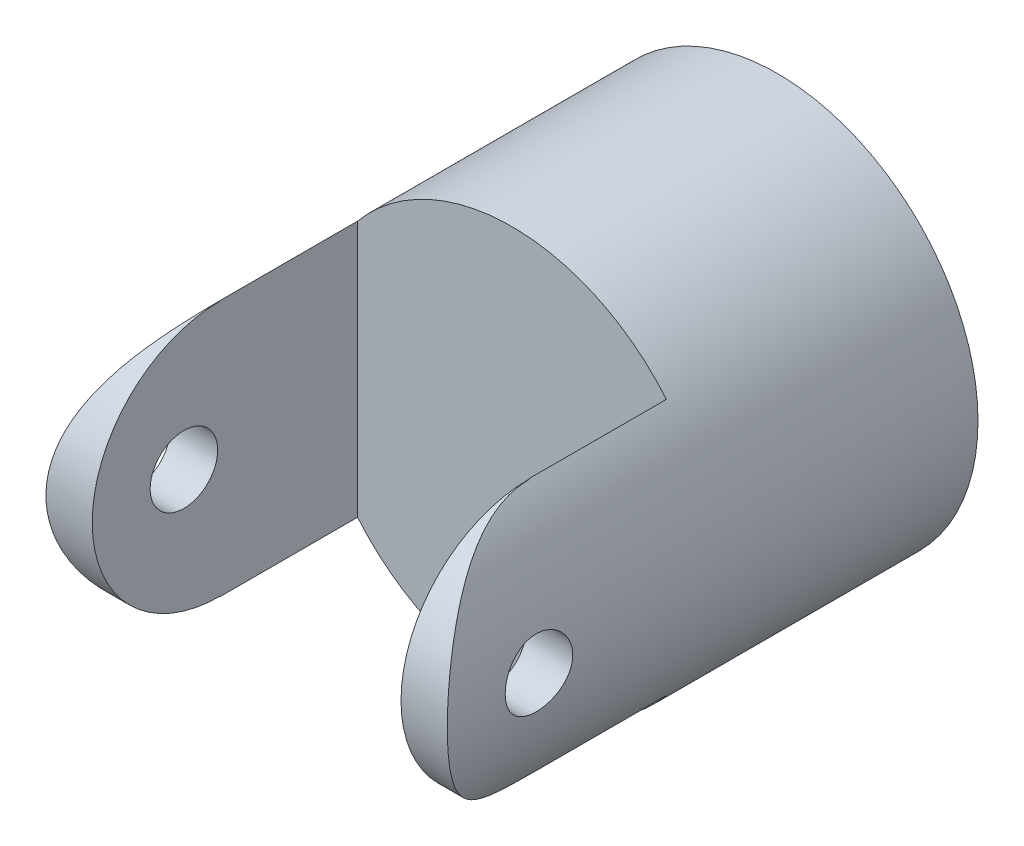
SolidWorks part; units mm, degrees
ref_plane "Front Plane" through (0, 0, 0) normal (0, 0, 1) x (1, 0, 0)
ref_plane "Top Plane" through (0, 0, 0) normal (0, 1, 0) x (1, 0, 0)
ref_plane "Right Plane" through (0, 0, 0) normal (1, 0, 0) x (0, 0, -1)
sketch "Sketch1" plane through (0, 0, 0) normal (0, 0, 1) x (1, 0, 0)
  circle A0 centre (0, 0) radius 4.16
  dimension "D1" = 8.32
extrude "Extrude1" add sketch "Sketch1" along normal blind 11
sketch "Sketch2" plane through (0, 0, 0) normal (0, 1, 0) x (1, 0, 0)
  line L0 (-4.16, 0) -> (-4.16, -11) construction
  line L1 (-3.2, -11.8574) -> (3.2, -11.8574)
  line L2 (-3.2, -11.8574) -> (-3.2, -5.5)
  line L3 (-3.2, -5.5) -> (3.2, -5.5)
  line L4 (3.2, -11.8574) -> (3.2, -5.5)
  line L5 (-4.16, -11) -> (4.16, -11) construction
  dimension "D1" = 6.4
  dimension "D2" = 0.96
  dimension "D3" = 5.5
extrude "Extrude2" cut sketch "Sketch2" against normal through all and the other way through all
sketch "Sketch3" plane through (0, 0, 0) normal (1, 0, 0) x (0, 0, -1)
  line L2 (-8.35, 2.65) -> (-8.35, 3.8367)
  line L4 (-8.35, -4.4922) -> (-12.8222, -4.6052)
  line L5 (-12.8222, -4.6052) -> (-12.8222, 3.8367)
  line L6 (-12.8222, 3.8367) -> (-8.35, 3.8367)
  line L8 (-8.35, -2.65) -> (-8.35, -4.4922)
  arc A0 (-8.35, 2.65) -> (-8.35, -2.65) centre (-8.35, 0) ccw
extrude "Extrude3" cut sketch "Sketch3" against normal through all and the other way through all
sketch "Sketch4" plane through (0, 0, 0) normal (1, 0, 0) x (0, 0, -1)
  circle A0 centre (-9.1, 0) radius 0.7
  dimension "D1" = 1.4
extrude "Extrude4" cut sketch "Sketch4" against normal through all and the other way through all
ref_axis "Axis1" through (3.2, 0, 9.1) along (1, 0, 0)
